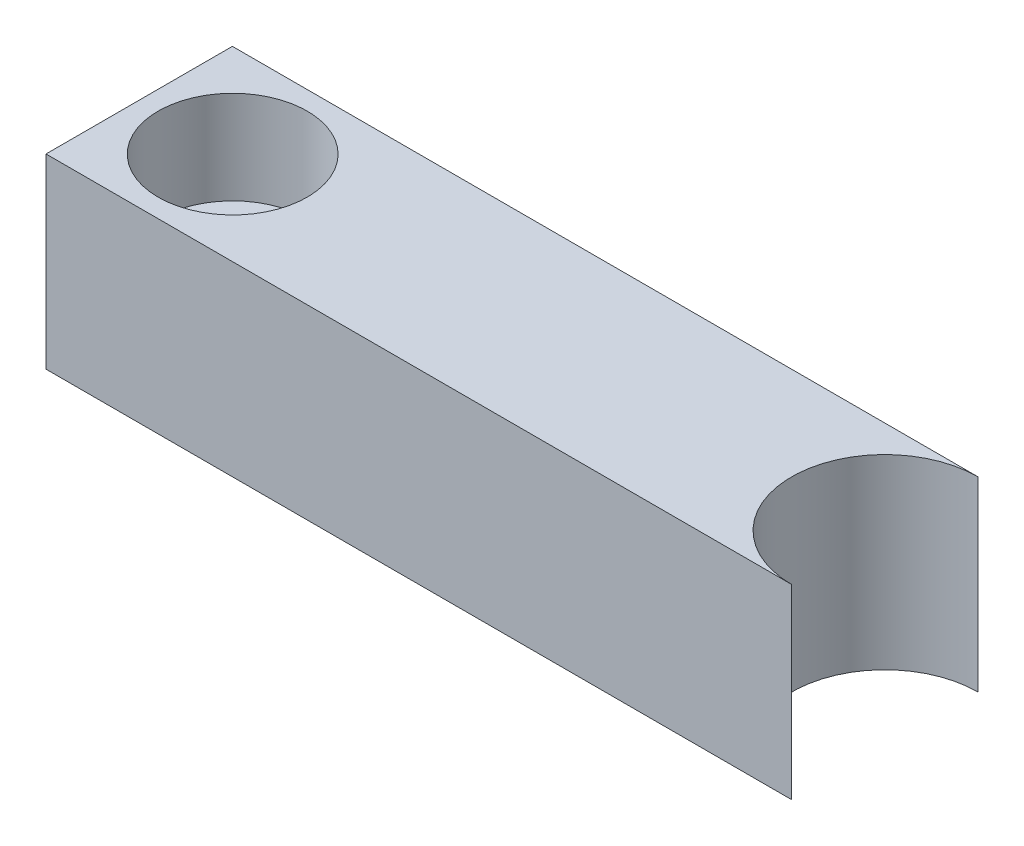
SolidWorks part; units mm, degrees
note: The reader was unsure of these and kept them because the rebuilt part matched: shared geometry of "Sketch1<6>", "Sketch1<8>".
ref_plane "Front Plane" through (0, 0, 0) normal (0, 0, 1) x (1, 0, 0)
ref_plane "Top Plane" through (0, 0, 0) normal (0, 1, 0) x (1, 0, 0)
ref_plane "Right Plane" through (0, 0, 0) normal (1, 0, 0) x (0, 0, -1)
sketch "Sketch1" plane through (0, 0, 0) normal (0, 1, 0) x (1, 0, 0)
  line L4 (-12.7, 1.5875) -> (-12.7, -1.5875)
  line L5 (0, 1.5875) -> (-12.7, 1.5875)
  line L7 (0, -1.5875) -> (-12.7, -1.5875)
  line L8 (-12.7, 1.5875) -> (-12.7, -1.5875)
  line L9 (-12.7, 1.5875) -> (-9.525, 1.5875)
  line L10 (-12.7, 1.5875) -> (-12.7, -1.5875)
  line L11 (-12.7, -1.5875) -> (-9.525, -1.5875)
  line L12 (-9.525, 1.5875) -> (-9.525, -1.5875)
  arc A0 (-2.7496, -1.5875) -> (-2.7496, 1.5875) centre (0, 0) ccw
  arc A1 (0, 1.5875) -> (0, -1.5875) centre (0, 0) ccw
  circle A2 centre (-11.1076, 0) radius 1.27
  dimension "D1" = 6.35
  dimension "D2" = 3.175
extrude "Boss-Extrude2" add sketch "Sketch1" along normal blind 3.175 contours A1 L5 L4 L7
extrude "Boss-Extrude6" add sketch "Sketch1<6>" along normal blind 3.175 contours L12 L5 L4 L7 A2
sketch "Sketch1<6>" plane through (0, 0, 0) normal (0, 1, 0) x (1, 0, 0) same geometry as "Sketch1"
extrude "Boss-Extrude7" add sketch "Sketch1<8>" along normal blind 1.5875 contours A2
sketch "Sketch1<8>" plane through (0, 0, 0) normal (0, 1, 0) x (1, 0, 0) same geometry as "Sketch1"
